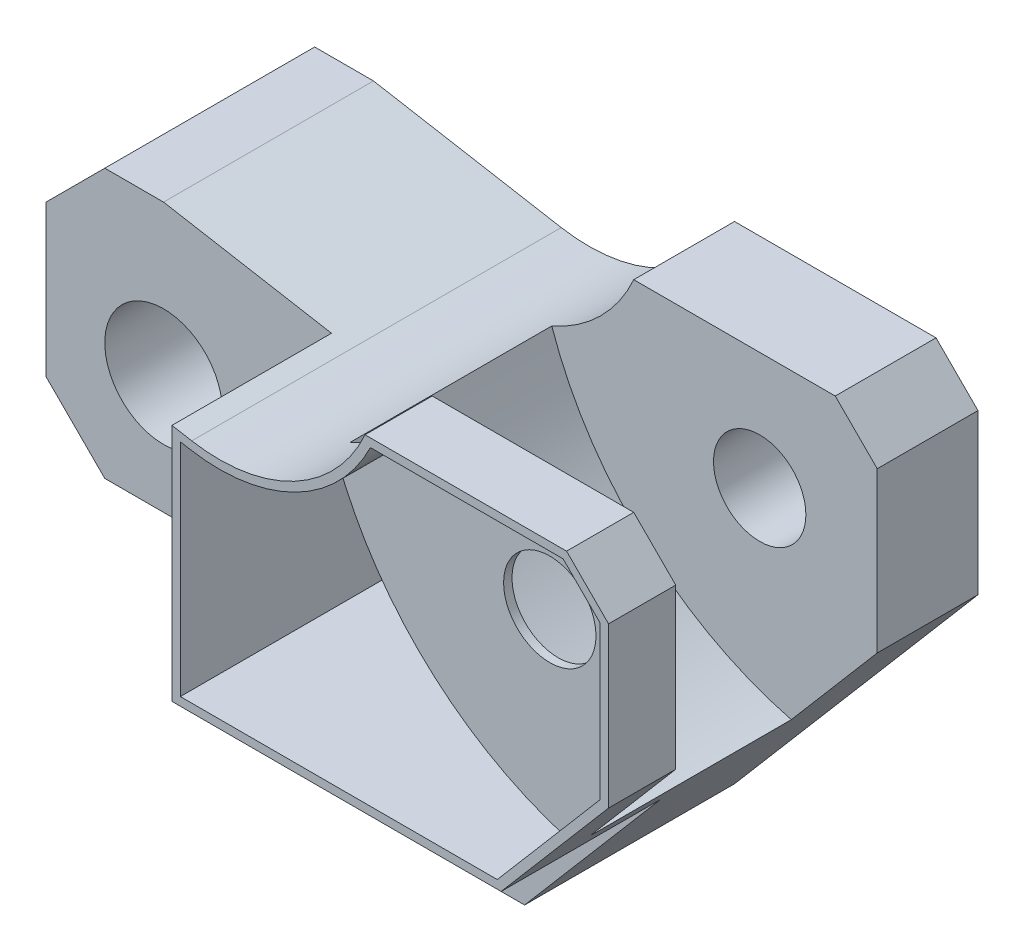
SolidWorks part; units mm, degrees
material "AISI 1020"
ref_plane "Front Plane" through (0, 0, 0) normal (0, 0, 1) x (1, 0, 0)
ref_plane "Top Plane" through (0, 0, 0) normal (0, 1, 0) x (1, 0, 0)
ref_plane "Right Plane" through (0, 0, 0) normal (1, 0, 0) x (0, 0, -1)
sketch "Sketch1" plane through (0, 0, 0) normal (0, 0, 1) x (1, 0, 0)
  line L0 (0, 0) -> (-7, 7)
  line L1 (-7, 7) -> (-7, 25)
  line L2 (-7, 25) -> (0, 32)
  line L6 (79, 34) -> (79, 15)
  line L7 (79, 15) -> (50, -19)
  line L8 (50, -19) -> (44.297, -19)
  line L9 (32.5755, 0) -> (0, 0)
  line L10 (79, 34) -> (74, 39)
  line L11 (74, 39) -> (50, 39)
  line L12 (0, 32) -> (7, 32)
  line L13 (7, 32) -> (29.3614, 28.0571)
  line L14 (7, -41.8607) -> (7, 32) construction
  line L15 (30.3211, 14) -> (-33.6507, 14) construction
  arc A2 (44.297, -19) -> (37.5212, -4.2647) centre (66.2059, 0) cw
  arc A4 (37.5212, -4.2647) -> (32.5755, 0) centre (32.5755, -5) ccw
  arc A5 (50, 39) -> (29.3614, 28.0571) centre (32.6607, 46.7684) cw
  circle A6 centre (7, 14) radius 7
  point P8 (47.1485, -19)
  point P20 (16.2878, 0)
  dimension "D5" = 29
  dimension "D6" = 5
  dimension "D14" = 19
  dimension "D21" = 14
  dimension "D2" = 7
  dimension "D3" = 45
  dimension "D4" = 19
  dimension "D7" = 29
  dimension "D8" = 19
  dimension "D9" = 24
  dimension "D10" = 45
  dimension "D11" = 5
  dimension "D12" = 29
  dimension "D13" = 58
  dimension "D15" = 10
  dimension "D17" = 32
  dimension "D16" = 45
  dimension "D18" = 86
  dimension "D19" = 14
  dimension "D20" = 14
extrude "Boss-Extrude1" add sketch "Sketch1" along normal mid plane 44
sketch "Sketch2" plane through (0, 0, 22) normal (0, 0, 1) x (1, 0, 0)
  line L0 (27, 0) -> (27, 28.4735)
  line L1 (0, 0) -> (32.5755, 0) construction
  line L2 (29.3614, 28.0571) -> (7, 32) construction
  line L3 (24.6138, 0) -> (27, 0)
  line L4 (50, -19) -> (79, 15) construction
  line L5 (79, 15) -> (79, 34) construction
  line L6 (74, 39) -> (50, 39) construction
  line L7 (44.297, -19) -> (50, -19) construction
  line L8 (-7, 7) -> (0, 0) construction
  line L9 (-7, 25) -> (-7, 7) construction
  line L10 (0, 32) -> (-7, 25) construction
  line L11 (7, 32) -> (0, 32) construction
  line L12 (50, -19) -> (66.2059, 0)
  line L13 (44.297, -19) -> (50, -19)
  line L14 (0, 0) -> (27, 0)
  line L15 (-7, 7) -> (0, 0)
  line L16 (-7, 25) -> (-7, 7)
  line L17 (0, 32) -> (-7, 25)
  line L18 (7, 32) -> (0, 32)
  line L19 (27, 28.4735) -> (7, 32)
  line L20 (32.5755, 0) -> (66.2059, 0)
  circle A0 centre (65, 25) radius 5.5
  arc A1 (37.5212, -4.2647) -> (32.5755, 0) centre (32.5755, -5) ccw construction
  arc A2 (37.5212, -4.2647) -> (44.297, -19) centre (66.2059, 0) ccw construction
  arc A3 (37.5212, -4.2647) -> (32.5755, 0) centre (32.5755, -5) ccw
  arc A4 (37.5212, -4.2647) -> (44.297, -19) centre (66.2059, 0) ccw
  line M3 (0, 0) -> (32.5755, 0)
  arc M4 (32.5755, 0) -> (37.5212, -4.2647) centre (32.5755, -5) cw
  arc M5 (37.5212, -4.2647) -> (44.297, -19) centre (66.2059, 0) ccw
  line M6 (44.297, -19) -> (50, -19)
  line M7 (50, -19) -> (79, 15)
  line M12 (29.3614, 28.0571) -> (7, 32)
  line M13 (7, 32) -> (0, 32)
  line M14 (0, 32) -> (-7, 25)
  line M15 (-7, 25) -> (-7, 7)
  line M16 (-7, 7) -> (0, 0)
  circle M17 centre (7, 14) radius 7
  dimension "D4" = 11
  dimension "D1" = 52
  dimension "D2" = 14
  dimension "D3" = 14
extrude "Cut-Extrude1" cut sketch "Sketch2" against normal blind 19 contours L0 M3 M12 M13 M14 M15 M16 M17 | L20 M4 M5 M6 M7 region at (25.8069, 0.4669, 22) region at (49.0899, -7.4639, 22)
extrude "Cut-Extrude2" cut sketch "Sketch2<3>" against normal through all contours A0
sketch "Sketch2<3>" plane through (0, 0, 22) normal (0, 0, 1) x (1, 0, 0) same geometry as "Sketch2"
sketch "Sketch3" plane through (0, 0, 0) normal (0, 0, 1) x (1, 0, 0)
  line L0 (66.2059, 0) -> (79, 15) construction
  line L1 (68.7647, 3) -> (79, 15)
  line L4 (74, 39) -> (50, 39) construction
  line L5 (79, 15) -> (79, 34) construction
  line L6 (79, 34) -> (74, 39) construction
  line L7 (79, 15) -> (79, 34)
  line L8 (79, 34) -> (74, 39)
  line L9 (74, 39) -> (50, 39)
  arc A1 (29.3614, 28.0571) -> (50, 39) centre (32.6607, 46.7684) ccw construction
  arc A2 (40.2369, 29.3443) -> (68.7647, 3) centre (79, 42.7019) ccw
  arc A3 (40.2369, 29.3443) -> (50, 39) centre (32.6607, 46.7684) ccw
  dimension "D1" = 36
  dimension "D2" = 41
extrude "Cut-Extrude3" cut sketch "Sketch3" against normal offset from surface 12 and the other way offset from surface 8 up to face at (70.5, 25, -22) other way up to face at (70.5, 25, 22)
sketch "Sketch4" plane through (0, 0, 22) normal (0, 0, 1) x (1, 0, 0)
  line L14 (29.1877, 27.0723) -> (28, 27.2817)
  line L15 (28, 27.2817) -> (28, 1)
  line L16 (28, 1) -> (65.7445, 1)
  line L17 (65.7445, 1) -> (78, 15.3685)
  line L18 (78, 15.3685) -> (78, 33.5858)
  line L19 (78, 33.5858) -> (73.5858, 38)
  line L20 (73.5858, 38) -> (50.6361, 38)
  line L21 (29.1877, 27.0723) -> (28, 27.2817)
  line L22 (28, 27.2817) -> (28, 1)
  line L23 (28, 1) -> (65.7445, 1)
  line L24 (65.7445, 1) -> (78, 15.3685)
  line L25 (78, 15.3685) -> (78, 33.5858)
  line L26 (78, 33.5858) -> (73.5858, 38)
  line L27 (73.5858, 38) -> (50.6361, 38)
  arc A2 (29.1877, 27.0723) -> (50.6361, 38) centre (32.6607, 46.7684) ccw
  arc A3 (29.1877, 27.0723) -> (50.6361, 38) centre (32.6607, 46.7684) ccw
  dimension "D1" = 1
extrude "Cut-Extrude4" cut sketch "Sketch4" against normal offset from surface (7 mm away) 1 up to face at (64.7646, 25.8067, 14)
sketch "Sketch5" plane through (0, 0, 15) normal (0, 0, 1) x (1, 0, 0)
  line L7 (29.1877, 27.0723) -> (28, 27.2817)
  line L8 (28, 27.2817) -> (28, 1)
  line L9 (28, 1) -> (65.7445, 1)
  line L10 (65.7445, 1) -> (78, 15.3685)
  line L11 (78, 15.3685) -> (78, 33.5858)
  line L12 (78, 33.5858) -> (73.5858, 38)
  line L13 (73.5858, 38) -> (50.6361, 38)
  line L14 (29.1877, 27.0723) -> (28, 27.2817)
  line L15 (28, 27.2817) -> (28, 1)
  line L16 (28, 1) -> (65.7445, 1)
  line L17 (65.7445, 1) -> (66.9868, 2.4566)
  arc A1 (29.1877, 27.0723) -> (50.6361, 38) centre (32.6607, 46.7684) ccw
  arc A2 (29.1877, 27.0723) -> (39.6467, 28.0282) centre (32.6607, 46.7684) ccw
  arc A4 (39.2915, 29.0185) -> (68.5151, 2.0317) centre (79, 42.7019) ccw
  arc A5 (39.6467, 28.0282) -> (66.9868, 2.4566) centre (79, 42.7019) ccw
  dimension "D1" = 0
  dimension "D2" = 1
extrude "Cut-Extrude5" cut sketch "Sketch5" against normal offset from surface (25 mm away) 12 up to face at (70.5, 25, -22)
equation "\"B\" = 58"
equation "\"A\" = 86"
equation "\"c\" = 44"
equation "\"D1@Boss-Extrude1\"= \"c\""
equation "\"D13@Sketch1\"=\"B\""
equation "\"D18@Sketch1\"=\"A\""
